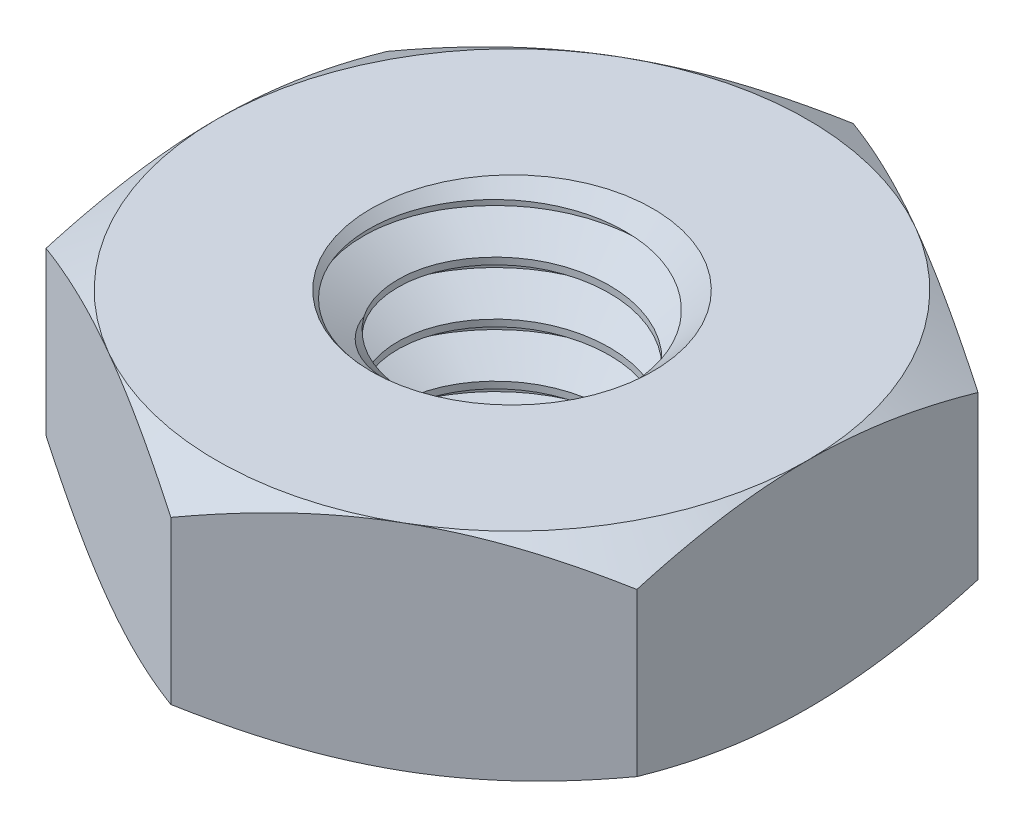
SolidWorks part; units mm, degrees
ref_plane "Front Plane" through (0, 0, 0) normal (0, 0, 1) x (1, 0, 0)
ref_plane "Top Plane" through (0, 0, 0) normal (0, 1, 0) x (1, 0, 0)
ref_plane "Right Plane" through (0, 0, 0) normal (1, 0, 0) x (0, 0, -1)
sketch "Sketch7" plane through (0, 0, 0) normal (0, 1, 0) x (1, 0, 0)
  line L0 (-4.3656, 0) -> (4.3656, 0) construction
  line L1 (-2.0828, 0) -> (2.0828, 0) construction
  line L2 (-4.3656, 0) -> (-4.3656, -0.7937) construction
  point P4 (0, 0)
  point P8 (0, 0)
sketch "Sketch6" plane through (0, 0, 0) normal (1, 0, 0) x (0, 0, -1)
  line L0 (0, 1.5875) -> (0, -1.5875) construction
  point P4 (0, 0)
sketch "Sketch1" plane through (0, 0, 0) normal (0, 1, 0) x (1, 0, 0)
  line L1 (-4.3656, 2.5205) -> (-4.3656, -2.5205)
  line L2 (-4.3656, -2.5205) -> (0, -5.041)
  line L3 (0, -5.041) -> (4.3656, -2.5205)
  line L4 (4.3656, -2.5205) -> (4.3656, 2.5205)
  line L5 (4.3656, 2.5205) -> (0, 5.041)
  line L6 (0, 5.041) -> (-4.3656, 2.5205)
  circle A0 centre (0, 0) radius 4.3656 construction
  circle A1 centre (0, 0) radius 2.0828
extrude "Boss-Extrude1" add sketch "Sketch1" along normal mid plane 3.175
sketch "Sketch5" plane through (0, 1.5875, 0) normal (0, 1, 0) x (1, 0, 0)
  circle A0 centre (0, 0) radius 4.3656 construction
  circle A1 centre (0, 0) radius 4.3656
extrude "Cut-Extrude2" cut sketch "Sketch5" against normal through all draft 60 flip side to cut
mirror "Mirror1" about plane through (0, 0, 0) normal (0, 1, 0) of "Cut-Extrude2"
sketch "Sketch14" plane through (0, 1.5875, 0) normal (0, 1, 0) x (1, 0, 0)
  line L0 (-2.0828, 0) -> (2.0828, 0) construction
  line L1 (0, 2.0828) -> (0, -2.0828) construction
  circle A0 centre (0, 0) radius 2.0828 construction
  point P7 (0, 0)
  point P11 (0, 0)
  point P12 (0, -2.0828)
  point P13 (-2.0828, 0)
  point P14 (0, 2.0828)
  point P15 (2.0828, 0)
sketch "Sketch8" plane through (0, 1.5875, 0) normal (0, 1, 0) x (1, 0, 0)
  circle A0 centre (0, 0) radius 2.0828 construction
  circle A1 centre (0, 0) radius 2.0828
extrude "Boss-Extrude2" add sketch "Sketch8" against normal up to surface (3.175 mm away) separate body up to face at (0, -1.5875, 0)
sketch "Sketch9" plane through (0, 1.5875, 0) normal (0, 1, 0) x (1, 0, 0)
  circle A0 centre (0, 0) radius 2.0828 construction
  circle A1 centre (0, 0) radius 2.0828
extrude "Boss-Extrude3" add sketch "Sketch9" against normal up to surface (3.175 mm away) up to face at (0, -1.5875, 0)
sketch "Sketch10" plane through (0, 1.5875, 0) normal (0, 1, 0) x (1, 0, 0)
  circle A0 centre (0, 0) radius 2.0828 construction
  circle A1 centre (0, 0) radius 2.0828
curve "Helix/Spiral1" pitch 0.7937 height 3.9688 radius 2.0828 centre (0, 1.5875, 0) axis (0, -1, 0) start towards (0, 0, 1)
sketch "Sketch11" plane through (0, 0, 0) normal (1, 0, 0) x (0, 0, -1)
  line L0 (-2.0828, 1.5875) -> (-2.0828, 2.282)
  line L1 (2.0828, 1.5875) -> (-2.0828, 1.5875) construction
  line L2 (-2.0828, 2.282) -> (-1.5672, 1.9844)
  line L3 (-1.5672, 1.9844) -> (-1.5672, 1.8852)
  line L4 (-1.5672, 1.8852) -> (-2.0828, 1.5875)
  line L5 (-2.0828, 1.9348) -> (-1.5672, 1.9348) construction
  line L6 (-1.825, 2.1332) -> (-1.825, 1.7363) construction
  spline S0 degree 3 poles (-2.0828, 1.5875) (-2.0828, 1.5711) (-1.9744, 1.5378) (-1.5111, 1.4883) (-0.8178, 1.4387) (0, 1.3891) (0.8178, 1.3395) (1.5111, 1.2898) (1.9744, 1.2402) (2.137, 1.1906) (1.9744, 1.141) (1.5111, 1.0914) (0.8178, 1.0418) (0, 0.9922) (-0.8178, 0.9426) (-1.5111, 0.893) (-1.9744, 0.8434) (-2.137, 0.7938) (-1.9744, 0.7441) (-1.5111, 0.6945) (-0.8178, 0.6449) (0, 0.5953) (0.8178, 0.5457) (1.5111, 0.4961) (1.9744, 0.4465) (2.137, 0.3969) (1.9744, 0.3473) (1.5111, 0.2977) (0.8178, 0.248) (0, 0.1984) (-0.8178, 0.1488) (-1.5111, 0.0992) (-1.9744, 0.0496) (-2.137, 0) (-1.9744, -0.0496) (-1.5111, -0.0992) (-0.8178, -0.1488) (0, -0.1984) (0.8178, -0.248) (1.5111, -0.2977) (1.9744, -0.3473) (2.137, -0.3969) (1.9744, -0.4465) (1.5111, -0.4961) (0.8178, -0.5457) (0, -0.5953) (-0.8178, -0.6449) (-1.5111, -0.6945) (-1.9744, -0.7441) (-2.137, -0.7938) (-1.9744, -0.8434) (-1.5111, -0.893) (-0.8178, -0.9426) (0, -0.9922) (0.8178, -1.0418) (1.5111, -1.0914) (1.9744, -1.141) (2.137, -1.1906) (1.9744, -1.2402) (1.5111, -1.2898) (0.8178, -1.3395) (0, -1.3891) (-0.8178, -1.4387) (-1.5111, -1.4883) (-1.9744, -1.5379) (-2.137, -1.5875) (-1.9744, -1.6371) (-1.5111, -1.6867) (-0.8178, -1.7363) (0, -1.7859) (0.8178, -1.8355) (1.5111, -1.8852) (1.9744, -1.9348) (2.137, -1.9844) (1.9744, -2.034) (1.5111, -2.0836) (0.8178, -2.1332) (0, -2.1828) (-0.8178, -2.2324) (-1.5111, -2.282) (-1.9744, -2.3316) (-2.0828, -2.3648) (-2.0828, -2.3813) knots 0 0 0 0 0.0125 0.025 0.0375 0.05 0.0625 0.075 0.0875 0.1 0.1125 0.125 0.1375 0.15 0.1625 0.175 0.1875 0.2 0.2125 0.225 0.2375 0.25 0.2625 0.275 0.2875 0.3 0.3125 0.325 0.3375 0.35 0.3625 0.375 0.3875 0.4 0.4125 0.425 0.4375 0.45 0.4625 0.475 0.4875 0.5 0.5125 0.525 0.5375 0.55 0.5625 0.575 0.5875 0.6 0.6125 0.625 0.6375 0.65 0.6625 0.675 0.6875 0.7 0.7125 0.725 0.7375 0.75 0.7625 0.775 0.7875 0.8 0.8125 0.825 0.8375 0.85 0.8625 0.875 0.8875 0.9 0.9125 0.925 0.9375 0.95 0.9625 0.975 0.9875 1 1 1 1 construction
  dimension "D1" = 60
  dimension "D2" = 0.0992
  dimension "D3" = 0.3969
sweep "Cut-Sweep1" cut profiles "Sketch11" path "Helix/Spiral1" align with end faces yes
combine bodies "Combine1" operation type subtract main body 107 bodies to subtract 108
sketch "Sketch12" plane through (0, 1.5875, 0) normal (0, 1, 0) x (1, 0, 0)
  circle A1 centre (0, 0) radius 2.0828
  circle A2 centre (0, 0) radius 2.0828
  dimension "D1" = 0
extrude "Cut-Extrude3" cut sketch "Sketch12" against normal through all draft 45
sketch "Sketch13" plane through (0, -1.5875, 0) normal (0, -1, 0) x (1, 0, 0)
  circle A1 centre (0, 0) radius 2.0828
  circle A2 centre (0, 0) radius 2.0828
  dimension "D1" = 0
extrude "Cut-Extrude4" cut sketch "Sketch13" against normal through all draft 45
ref_axis "Nut Hex 8-32 Axis" through (0, -1.5875, 0) along (0, 1, 0)
equation "\"D3@Helix/Spiral1\"=\"Thickness@Sketch6\"+\"Pitch@Sketch7\""
equation "\"Height@Boss-Extrude1\"=\"Thickness@Sketch6\""
equation "\"D4@Helix/Spiral1\"=\"Pitch@Sketch7\""
equation "\"D2@Sketch11\"=\"Pitch@Sketch7\"*.125"
equation "\"D3@Sketch11\"=\"Pitch@Sketch7\"*.5"
